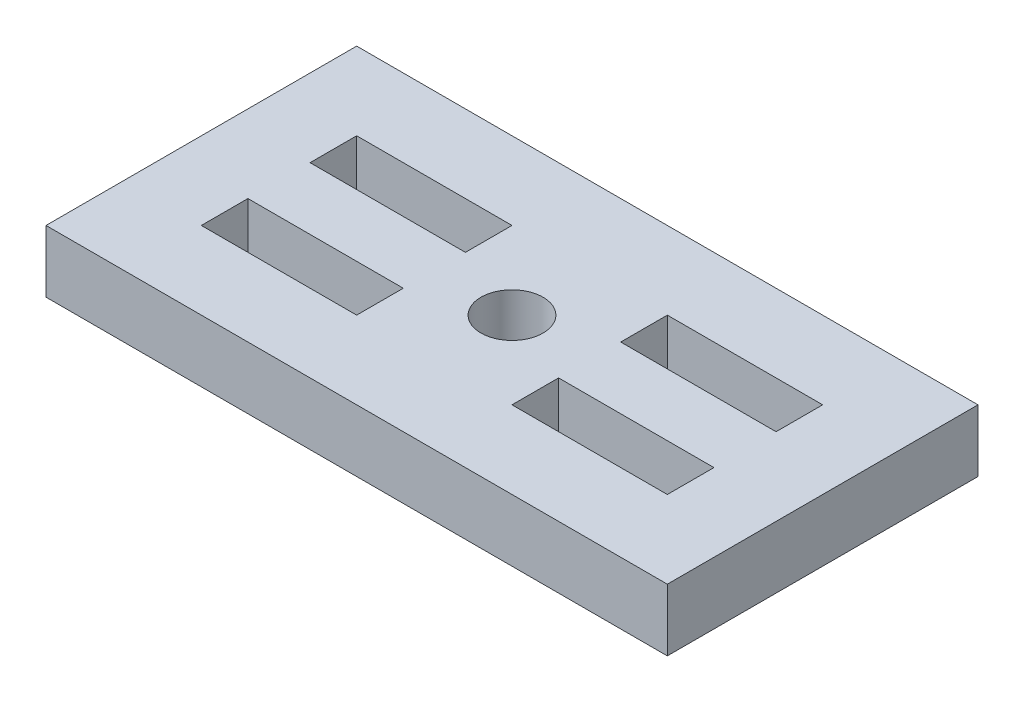
SolidWorks part; units mm, degrees
ref_plane "Front Plane" through (0, 0, 0) normal (0, 0, 1) x (1, 0, 0)
ref_plane "Top Plane" through (0, 0, 0) normal (0, 1, 0) x (1, 0, 0)
ref_plane "Right Plane" through (0, 0, 0) normal (1, 0, 0) x (0, 0, -1)
sketch "Sketch1" plane through (0, 0, 0) normal (0, 1, 0) x (1, 0, 0)
  line L1 (-7.7249, 4.6296) -> (12.2751, 4.6296)
  line L2 (-7.7249, 4.6296) -> (-7.7249, -5.3704)
  line L3 (-7.7249, -5.3704) -> (12.2751, -5.3704)
  line L4 (12.2751, 4.6296) -> (12.2751, -5.3704)
  dimension "D1" = 10
  dimension "D2" = 20
extrude "Boss-Extrude1" add sketch "Sketch1" along normal blind 2
sketch "Sketch2" plane through (0, 2, 0) normal (0, 1, 0) x (1, 0, 0)
  line L4 (12.2751, 4.6296) -> (-7.7249, 4.6296) construction
  line L5 (2.2751, 4.6296) -> (2.2751, -5.3704) construction
  line L6 (-7.7249, -0.3704) -> (12.2751, -0.3704) construction
  line L7 (-7.7249, 4.6296) -> (-7.7249, -5.3704) construction
  line L8 (12.2751, -5.3704) -> (12.2751, 4.6296) construction
  circle A0 centre (2.2751, -0.3704) radius 1
  dimension "D1" = 2
sketch "Sketch3" plane through (0, 2, 0) normal (0, 1, 0) x (1, 0, 0)
  line L0 (2.2751, 4.6296) -> (2.2751, -5.3704) construction
  line L1 (-5.2249, 2.1296) -> (-0.2249, 2.1296)
  line L2 (-5.2249, 2.1296) -> (-5.2249, 0.6296)
  line L3 (-5.2249, 0.6296) -> (-0.2249, 0.6296)
  line L4 (-0.2249, 2.1296) -> (-0.2249, 0.6296)
  line L5 (4.7751, 0.6296) -> (9.7751, 0.6296)
  line L6 (4.7751, 0.6296) -> (4.7751, 2.1296)
  line L7 (4.7751, 2.1296) -> (9.7751, 2.1296)
  line L8 (9.7751, 0.6296) -> (9.7751, 2.1296)
  line L9 (9.7751, -2.8704) -> (4.7751, -2.8704)
  line L10 (9.7751, -2.8704) -> (9.7751, -1.3704)
  line L11 (9.7751, -1.3704) -> (4.7751, -1.3704)
  line L12 (4.7751, -2.8704) -> (4.7751, -1.3704)
  line L13 (-0.2249, -2.8704) -> (-5.2249, -2.8704)
  line L14 (-0.2249, -2.8704) -> (-0.2249, -1.3704)
  line L15 (-0.2249, -1.3704) -> (-5.2249, -1.3704)
  line L16 (-5.2249, -2.8704) -> (-5.2249, -1.3704)
  line L17 (-7.7249, -0.3704) -> (12.2751, -0.3704) construction
  point P16 (-0.2249, 1.3796)
  dimension "D1" = 5
  dimension "D2" = 2.5
  dimension "D3" = 2
  dimension "D4" = 1
  dimension "D5" = 1.5
  dimension "D6" = 5
extrude "Cut-Extrude1" cut sketch "Sketch3" against normal blind 2
extrude "Cut-Extrude2" cut sketch "Sketch2" against normal blind 2 contours A0
